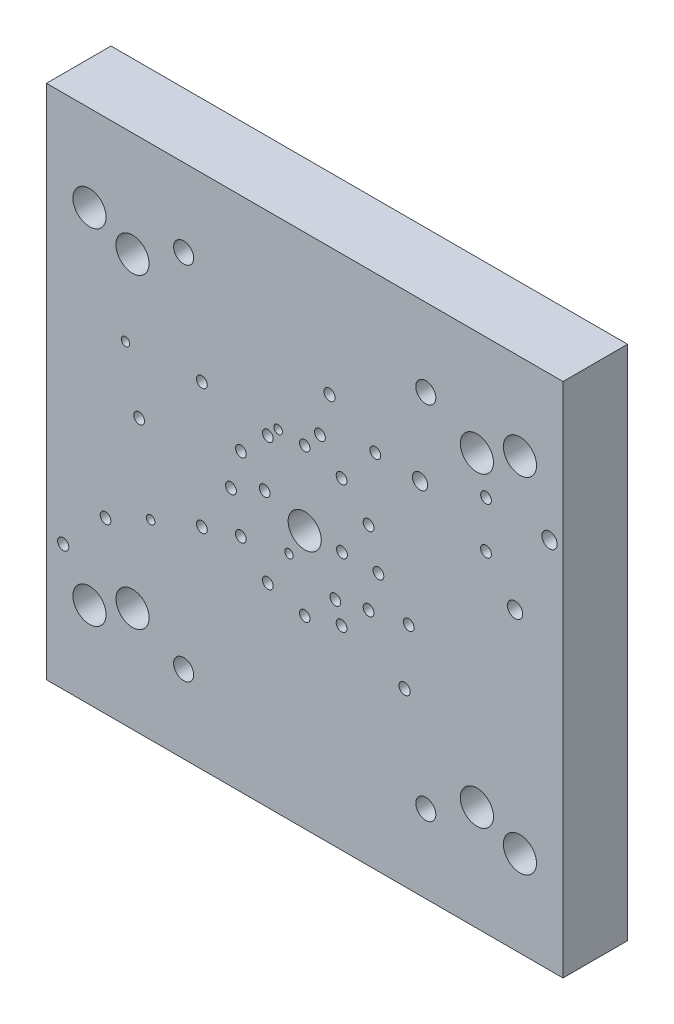
SolidWorks part; units mm, degrees
ref_plane "Front Plane" through (0, 0, 0) normal (0, 0, 1) x (1, 0, 0)
ref_plane "Top Plane" through (0, 0, 0) normal (0, 1, 0) x (1, 0, 0)
ref_plane "Right Plane" through (0, 0, 0) normal (1, 0, 0) x (0, 0, -1)
sketch "Sketch1" plane through (0, 0, 0) normal (0, 0, 1) x (1, 0, 0)
  line L1 (-152.4, 152.4) -> (152.4, 152.4)
  line L2 (-152.4, 152.4) -> (-152.4, -152.4)
  line L3 (-152.4, -152.4) -> (152.4, -152.4)
  line L4 (152.4, 152.4) -> (152.4, -152.4)
  line L5 (-152.4, 152.4) -> (152.4, -152.4) construction
  line L6 (-152.4, -152.4) -> (152.4, 152.4) construction
  point P0 (0, 0)
  dimension "D1" = 304.8
  dimension "D2" = 304.8
extrude "Boss-Extrude1" add sketch "Sketch1" along normal blind 38.1
sketch "Sketch2" plane through (0, 0, 38.1) normal (0, 0, 1) x (1, 0, 0)
  line L0 (-152.4, 0) -> (152.4, 0) construction
  line L5 (-152.4, 152.4) -> (-152.4, -152.4) construction
  line L6 (152.4, -152.4) -> (152.4, 152.4) construction
  line L7 (-152.4, -101.6) -> (152.4, -101.6) construction
  line L8 (-152.4, 101.6) -> (152.4, 101.6) construction
  line L9 (0, 101.6) -> (0, -101.6) construction
  line L10 (127, 101.6) -> (127, -101.6) construction
  line L11 (-127, 101.6) -> (-127, -101.6) construction
  circle A0 centre (-127, 101.6) radius 6.5151
  circle A1 centre (127, 101.6) radius 6.5151
  circle A2 centre (127, -101.6) radius 6.5151
  circle A3 centre (-127, -101.6) radius 6.5151
  circle A4 centre (0, 0) radius 6.5151
  dimension "D5" = 13.0302
  dimension "D1" = 101.6
  dimension "D2" = 101.6
  dimension "D3" = 127
  dimension "D4" = 127
extrude "HAAS T-Slot Holes" cut sketch "Sketch2" against normal through all
sketch "Sketch3" plane through (0, 0, 38.1) normal (0, 0, 1) x (1, 0, 0)
  circle A0 centre (-127, 101.6) radius 9.779
  circle A1 centre (127, 101.6) radius 9.779
  circle A2 centre (0, 0) radius 9.779
  circle A3 centre (127, -101.6) radius 9.779
  circle A4 centre (-127, -101.6) radius 9.779
  dimension "D1" = 19.558
extrude "HAAS Counter Bores" cut sketch "Sketch3" against normal offset from surface (22.225 mm away) 15.875 contours A0 | A1 | A2 | A3 | A4 up to face at (6.5151, 0, 0)
sketch "Sketch4" plane through (0, 0, 38.1) normal (0, 0, 1) x (1, 0, 0)
  line L0 (-127, 90.4875) -> (127, 90.4875) construction
  line L1 (-127, 30.1625) -> (127, 30.1625) construction
  line L2 (-127, 30.1625) -> (-127, -30.1625) construction
  line L3 (-127, -30.1625) -> (127, -30.1625) construction
  line L4 (127, 30.1625) -> (127, -30.1625) construction
  line L5 (-127, 30.1625) -> (127, -30.1625) construction
  line L6 (-127, -30.1625) -> (127, 30.1625) construction
  line L7 (-127, -90.4875) -> (127, -90.4875) construction
  line L8 (-101.6, 90.4875) -> (-101.6, 84.1375) construction
  line L9 (-101.6, -90.4875) -> (-101.6, -84.1375) construction
  line L10 (101.6, -90.4875) -> (101.6, -84.1375) construction
  line L11 (101.6, 90.4875) -> (101.6, 84.1375) construction
  circle A0 centre (-101.6, 90.4875) radius 6.5151
  circle A1 centre (101.6, 90.4875) radius 6.5151
  circle A2 centre (-101.6, -90.4875) radius 6.5151
  circle A3 centre (101.6, -90.4875) radius 6.5151
  point P0 (0, 0)
  dimension "D9" = 13.0302
  dimension "D1" = 60.325
  dimension "D2" = 254
  dimension "D5" = 203.2
  dimension "D6" = 25.4
  dimension "D7" = 203.2
  dimension "D8" = 6.35
  dimension "D3" = 60.325
  dimension "D4" = 60.325
extrude "Tormach T-Slot Holes" cut sketch "Sketch4" against normal through all
sketch "Sketch5" plane through (0, 0, 38.1) normal (0, 0, 1) x (1, 0, 0)
  circle A0 centre (-101.6, 90.4875) radius 9.779
  circle A1 centre (101.6, 90.4875) radius 9.779
  circle A2 centre (101.6, -90.4875) radius 9.779
  circle A3 centre (-101.6, -90.4875) radius 9.779
  dimension "D1" = 19.558
extrude "Tormach Counter bores" cut sketch "Sketch5" against normal up to surface (22.225 mm away) up to face at (-117.221, 101.6, 15.875)
sketch "Sketch6" plane through (0, 0, 38.1) normal (0, 0, 1) x (1, 0, 0)
  circle A0 centre (0, 0) radius 43.5 construction
  circle A1 centre (0, 43.5) radius 3.0734
  circle A2 centre (0, -43.5) radius 3.0734
  dimension "D1" = 87.0001
  dimension "D2" = 6.1468
extrude "Sprocket Locating Holes" cut sketch "Sketch6" against normal blind 6.35
sketch "Sketch7" plane through (0, 0, 38.1) normal (0, 0, 1) x (1, 0, 0)
  circle A0 centre (0, 0) radius 43.5 construction
  circle A2 centre (43.5, 0) radius 3.175
  circle A4 centre (37.6721, -21.75) radius 3.175
  circle A5 centre (21.75, -37.6721) radius 3.175
  circle A6 centre (0, -43.5) radius 3.175 [skipped]
  circle A7 centre (-21.75, -37.6721) radius 3.175
  circle A8 centre (-37.6721, -21.75) radius 3.175
  circle A9 centre (-43.5, 0) radius 3.175
  circle A10 centre (-37.6721, 21.75) radius 3.175
  circle A11 centre (-21.75, 37.6721) radius 3.175
  circle A12 centre (0, 43.5) radius 3.175 [skipped]
  circle A13 centre (21.75, 37.6721) radius 3.175
  circle A14 centre (37.6721, 21.75) radius 3.175
  point P31 (0, 0)
  dimension "D1" = 87.0001
  dimension "D2" = 6.35
  dimension "D3" = 12
extrude "Sprocket Mounting clearance holes" cut sketch "Sketch7" against normal blind 9.525
sketch "Sketch8" plane through (0, 0, 38.1) normal (0, 0, 1) x (1, 0, 0)
  line L1 (-71.4375, 106.4641) -> (71.4375, 106.4641) construction
  line L2 (-71.4375, 106.4641) -> (-71.4375, -106.4641) construction
  line L3 (-71.4375, -106.4641) -> (71.4375, -106.4641) construction
  line L4 (71.4375, 106.4641) -> (71.4375, -106.4641) construction
  line L5 (-71.4375, 106.4641) -> (71.4375, -106.4641) construction
  line L6 (-71.4375, -106.4641) -> (71.4375, 106.4641) construction
  circle A0 centre (-71.4375, 106.4641) radius 5.9182
  circle A1 centre (71.4375, 106.4641) radius 5.9182
  circle A2 centre (71.4375, -106.4641) radius 5.9182
  circle A3 centre (-71.4375, -106.4641) radius 5.9182
  point P0 (0, 0)
  dimension "D3" = 11.8364
  dimension "D1" = 142.875
  dimension "D2" = 212.9282
extrude "1/2-13 Tapped Holes" cut sketch "Sketch8" against normal blind 19.05
sketch "Sketch9" plane through (0, 0, 38.1) normal (0, 0, 1) x (1, 0, 0)
  circle A0 centre (-117.5189, -52.2876) radius 3.175
  circle A1 centre (-60.6634, -28.4101) radius 3.175
  circle A2 centre (-60.6634, 45.677) radius 3.175
  circle A3 centre (-23.6198, 8.6335) radius 3.175
  circle A4 centre (-97.707, 8.6335) radius 3.175
  circle A5 centre (18.0623, -26.1797) radius 3.175
  circle A6 centre (21.9762, 0) radius 3.175
  circle A7 centre (61.3833, -17.3739) radius 3.175
  circle A8 centre (106.976, 70.3959) radius 3.175
  circle A9 centre (106.976, 42.9004) radius 3.175
  circle A10 centre (144.4539, 67.4373) radius 4.5
  circle A11 centre (124.1092, 21.6131) radius 4.5
  circle A12 centre (68.0681, 59.3279) radius 4.5
  circle A13 centre (58.9353, -51.2652) radius 3.3
  circle A14 centre (-142.4923, -78.095) radius 3.3
  circle A15 centre (-105.7351, 43.7713) radius 2.5
  circle A16 centre (-90.8975, -39.8642) radius 2.5
  circle A17 centre (-9.2711, -16.3656) radius 2.5
  circle A18 centre (-15.6655, 43.8657) radius 2.5
  circle A20 centre (14.6267, 76.8405) radius 3.3
  circle A21 centre (8.9855, 53.4682) radius 3.175
  circle A22 centre (41.6559, 60.6579) radius 3.175
extrude "Cut-Extrude1" cut sketch "Sketch9" against normal blind 19.05
